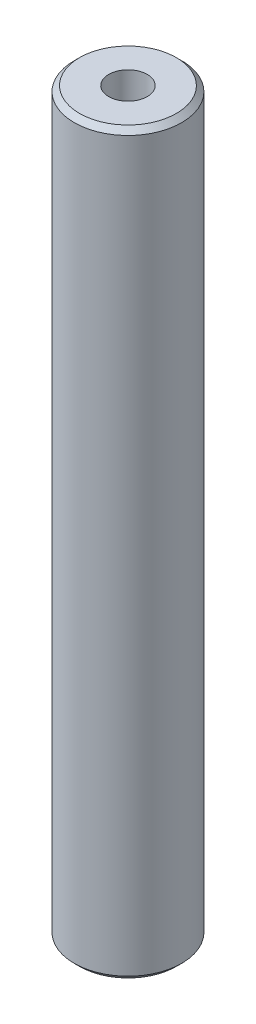
SolidWorks part; units mm, degrees
ref_plane "Front Plane" through (0, 0, 0) normal (0, 0, 1) x (1, 0, 0)
ref_plane "Top Plane" through (0, 0, 0) normal (0, 1, 0) x (1, 0, 0)
ref_plane "Right Plane" through (0, 0, 0) normal (1, 0, 0) x (0, 0, -1)
sketch "Sketch1" plane through (0, 0, 0) normal (0, 1, 0) x (1, 0, 0)
  circle A0 centre (0, 0) radius 17.5
  dimension "SHAFT_OD" = 35
extrude "Boss-Extrude1" add sketch "Sketch1" along normal blind 240.6577
sketch "Sketch2" plane through (0, 0, 0) normal (0, 1, 0) x (1, 0, 0)
  circle A0 centre (0, 0) radius 6.2781
  dimension "BORE_D" = 12.5563
extrude "Cut-Extrude1" cut sketch "Sketch2" along normal through all
chamfer "Chamfer1" distance 1.7302 angle 45 2 edges at (0, 240.6577, 17.5) (0, 0, 17.5)
